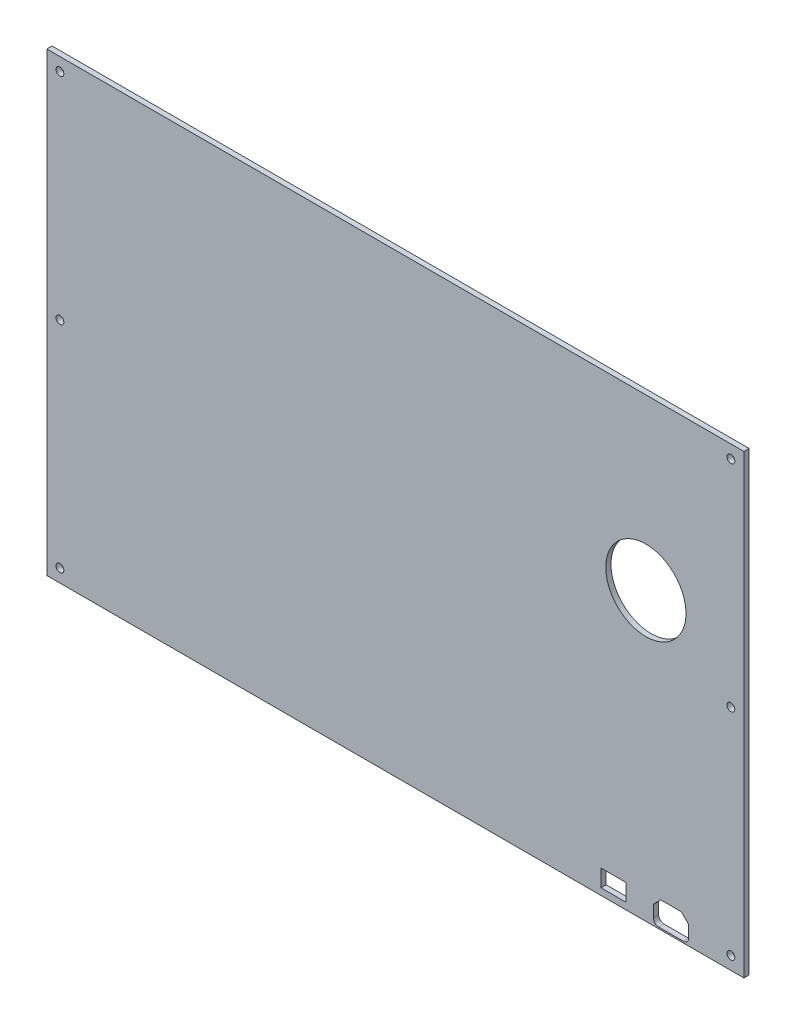
SolidWorks part; units mm, degrees
material "Sklo"
ref_plane "Přední rovina" through (0, 0, 0) normal (0, 0, 1) x (1, 0, 0)
ref_plane "Horní rovina" through (0, 0, 0) normal (0, 1, 0) x (1, 0, 0)
ref_plane "Pravá rovina" through (0, 0, 0) normal (1, 0, 0) x (0, 0, -1)
sketch "Skica1" plane through (0, 0, 0) normal (0, 0, 1) x (1, 0, 0)
  line L1 (267.5, -175) -> (-267.5, -175)
  line L2 (267.5, -175) -> (267.5, 175)
  line L3 (267.5, 175) -> (-267.5, 175)
  line L4 (-267.5, -175) -> (-267.5, 175)
  line L5 (267.5, -175) -> (-267.5, 175) construction
  line L6 (267.5, 175) -> (-267.5, -175) construction
  circle A0 centre (-257.5, 165) radius 3
  circle A1 centre (-257.5, 0) radius 3
  circle A2 centre (-257.5, -165) radius 3
  circle A3 centre (257.5, 165) radius 3
  circle A4 centre (257.5, 0) radius 3
  circle A5 centre (257.5, -165) radius 3
  point P0 (0, 0)
  point P12 (-267.5, 0)
  dimension "D3" = 6
  dimension "D1" = 535
  dimension "D2" = 350
  dimension "D4" = 10
  dimension "D5" = 10
  dimension "D6" = 10
  dimension "D7" = 10
  dimension "D8" = 10
  dimension "D9" = 2
extrude "Přidat vysunutím1" add sketch "Skica1" along normal blind 4
sketch "Skica2" plane through (0, 0, 0) normal (0, 0, -1) x (-1, 0, 0)
  circle A0 centre (-192.2483, 45.046) radius 30.7767
extrude "Odebrat vysunutím1" cut sketch "Skica2" against normal blind 4
sketch "Skica3" plane through (0, 0, 4) normal (0, 0, 1) x (1, 0, 0)
  line L0 (203.8717, -155) -> (209.0646, -155) construction
  line L1 (157.8146, -156.78) -> (176.9646, -156.78)
  line L2 (157.8146, -156.78) -> (157.8146, -169.89)
  line L3 (157.8146, -169.89) -> (176.9646, -169.89)
  line L4 (176.9646, -156.78) -> (176.9646, -169.89)
  line L5 (209.0646, -155) -> (214.0646, -155) construction
  line L6 (214.0646, -155) -> (219.2575, -155) construction
  line L7 (203.5181, -155.1464) -> (198.211, -160.4536) construction
  line L8 (224.9181, -160.4536) -> (219.611, -155.1464) construction
  line L9 (225.0646, -169.8) -> (225.0646, -160.8071) construction
  line L10 (202.0646, -173.8) -> (221.0646, -173.8) construction
  line L11 (216.0646, -173.8) -> (207.0646, -173.8) construction
  line L12 (207.0646, -173.8) -> (202.0646, -173.8) construction
  line L13 (198.0646, -160.8071) -> (198.0646, -169.8) construction
  line L14 (203.8717, -155) -> (209.0646, -155)
  line L15 (209.0646, -155) -> (214.0646, -155)
  line L16 (214.0646, -155) -> (219.2575, -155)
  line L17 (203.5181, -155.1464) -> (198.211, -160.4536)
  line L18 (224.9181, -160.4536) -> (219.611, -155.1464)
  line L19 (225.0646, -169.8) -> (225.0646, -160.8071)
  line L20 (202.0646, -173.8) -> (221.0646, -173.8)
  line L21 (216.0646, -173.8) -> (207.0646, -173.8)
  line L22 (207.0646, -173.8) -> (202.0646, -173.8)
  line L23 (198.0646, -160.8071) -> (198.0646, -169.8)
  arc A0 (203.8717, -155) -> (203.5181, -155.1464) centre (203.8717, -155.5) ccw construction
  arc A1 (219.611, -155.1464) -> (219.2575, -155) centre (219.2575, -155.5) ccw construction
  arc A2 (225.0646, -160.8071) -> (224.9181, -160.4536) centre (224.5646, -160.8071) ccw construction
  arc A3 (198.211, -160.4536) -> (198.0646, -160.8071) centre (198.5646, -160.8071) ccw construction
  arc A4 (221.0646, -173.8) -> (225.0646, -169.8) centre (221.0646, -169.8) ccw construction
  arc A5 (198.0646, -169.8) -> (202.0646, -173.8) centre (202.0646, -169.8) ccw construction
  arc A6 (203.8717, -155) -> (203.5181, -155.1464) centre (203.8717, -155.5) ccw
  arc A7 (219.611, -155.1464) -> (219.2575, -155) centre (219.2575, -155.5) ccw
  arc A8 (225.0646, -160.8071) -> (224.9181, -160.4536) centre (224.5646, -160.8071) ccw
  arc A9 (198.211, -160.4536) -> (198.0646, -160.8071) centre (198.5646, -160.8071) ccw
  arc A10 (221.0646, -173.8) -> (225.0646, -169.8) centre (221.0646, -169.8) ccw
  arc A11 (198.0646, -169.8) -> (202.0646, -173.8) centre (202.0646, -169.8) ccw
extrude "Odebrat vysunutím2" cut sketch "Skica3" against normal blind 4 contours L23 A11 L20 A10 L19 A8 L18 A7 L16 L15 L14 A6 L17 A9 | L4 L1 L2 L3 region at (167.3896, -163.335, 4) region at (211.5646, -164.7792, 4)
